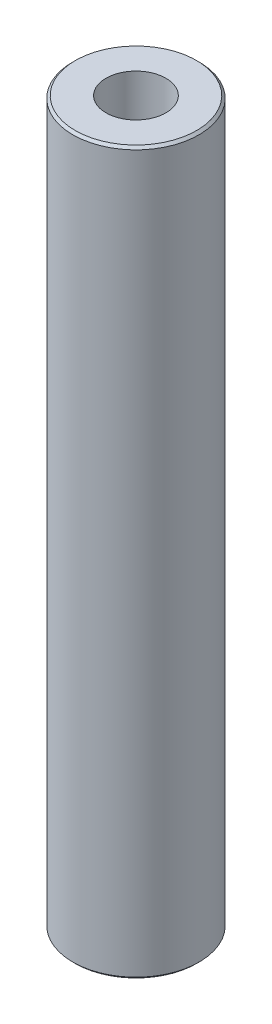
SolidWorks part; units mm, degrees
ref_plane "Front Plane" through (0, 0, 0) normal (0, 0, 1) x (1, 0, 0)
ref_plane "Top Plane" through (0, 0, 0) normal (0, 1, 0) x (1, 0, 0)
ref_plane "Right Plane" through (0, 0, 0) normal (1, 0, 0) x (0, 0, -1)
sketch "Sketch1" plane through (0, 0, 0) normal (0, 1, 0) x (1, 0, 0)
  circle A0 centre (0, 0) radius 52.5
  dimension "SHAFT_OD" = 105
extrude "Boss-Extrude1" add sketch "Sketch1" along normal blind 600
sketch "Sketch2" plane through (0, 0, 0) normal (0, 1, 0) x (1, 0, 0)
  circle A0 centre (0, 0) radius 24.9432
  dimension "BORE_D" = 49.8864
extrude "Cut-Extrude1" cut sketch "Sketch2" along normal through all
chamfer "Chamfer1" distance 2.0336 angle 45 2 edges at (0, 600, 52.5) (0, 0, 52.5)
